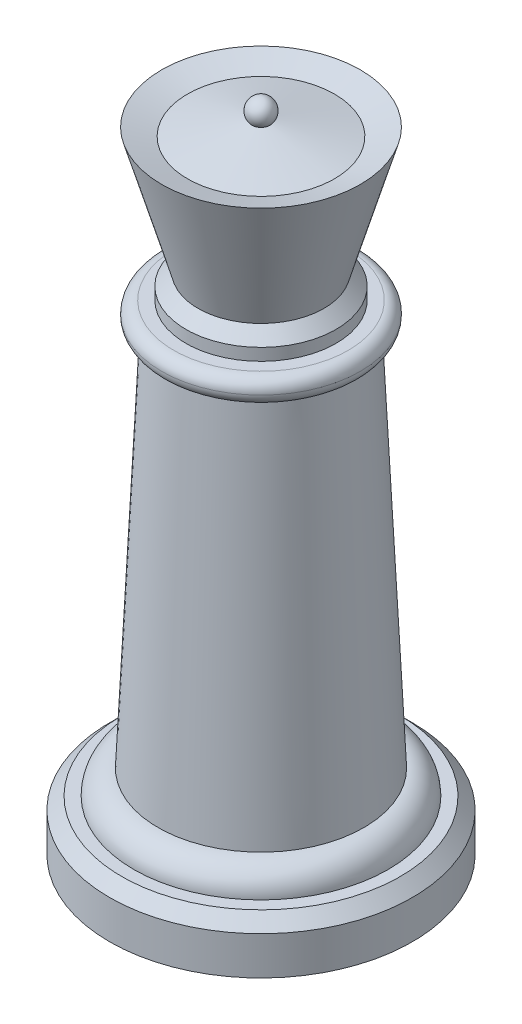
SolidWorks part; units mm, degrees
ref_plane "Front Plane" through (0, 0, 0) normal (0, 0, 1) x (1, 0, 0)
ref_plane "Top Plane" through (0, 0, 0) normal (0, 1, 0) x (1, 0, 0)
ref_plane "Right Plane" through (0, 0, 0) normal (1, 0, 0) x (0, 0, -1)
sketch "Sketch1" plane through (0, 0, 0) normal (0, 0, 1) x (1, 0, 0)
  line L0 (0, 0) -> (0, 41.275) construction
  line L1 (-6.477, 3.175) -> (-6.477, 4.699) construction
  line L2 (0, 0) -> (-9.525, 0)
  line L4 (-8.001, 3.175) -> (-9.525, 3.175)
  line L5 (-9.525, 0) -> (-9.525, 3.175)
  line L8 (-6.477, 4.699) -> (-8.001, 4.699)
  line L9 (-8.001, 3.175) -> (-8.001, 4.699)
  line L10 (-3.9624, 30.2006) -> (-3.9624, 31.7246) construction
  line L11 (-5.3848, 28.6766) -> (-6.2484, 28.6766)
  line L13 (-4.7244, 30.2006) -> (-6.2484, 30.2006)
  line L14 (-6.2484, 28.6766) -> (-6.2484, 30.2006)
  line L17 (-3.9624, 31.7246) -> (-4.7244, 31.7246)
  line L18 (-4.7244, 30.2006) -> (-4.7244, 31.7246)
  line L19 (-6.477, 4.699) -> (-5.3848, 28.6766)
  line L20 (-3.9624, 31.7246) -> (-6.2484, 39.624)
  line L21 (-6.2484, 39.624) -> (-4.6228, 39.116)
  line L22 (-4.6228, 39.116) -> (-0.5696, 40.0068)
  line L23 (0, 0) -> (0, 41.275)
  arc A0 (0, 41.275) -> (-0.5696, 40.0068) centre (0, 40.513) ccw
  point P4 (-6.2484, 39.624)
  point P11 (-4.6228, 39.116)
  point P13 (0, 40.132)
  dimension "D6" = 1.524
  dimension "D1" = 41.275
  dimension "D2" = 9.525
  dimension "D3" = 3.175
  dimension "D4" = 1.524
  dimension "D5" = 1.524
  dimension "D7" = 1.524
  dimension "D8" = 1.524
  dimension "D9" = 1.524
  dimension "D10" = 28.6766
revolve "Revolve1" add sketch "Sketch1" angle 360 about L23
chamfer "Chamfer1" distance 0.762 angle 45 2 edges at (0, 31.7246, -4.7244) (0, 3.175, -9.525)
fillet "Fillet1" radius 1.524 1 edges at (0, 4.699, -8.001)
fillet "Fillet2" radius 0.762 2 edges at (0, 30.2006, -6.2484) (0, 28.6766, -6.2484)
